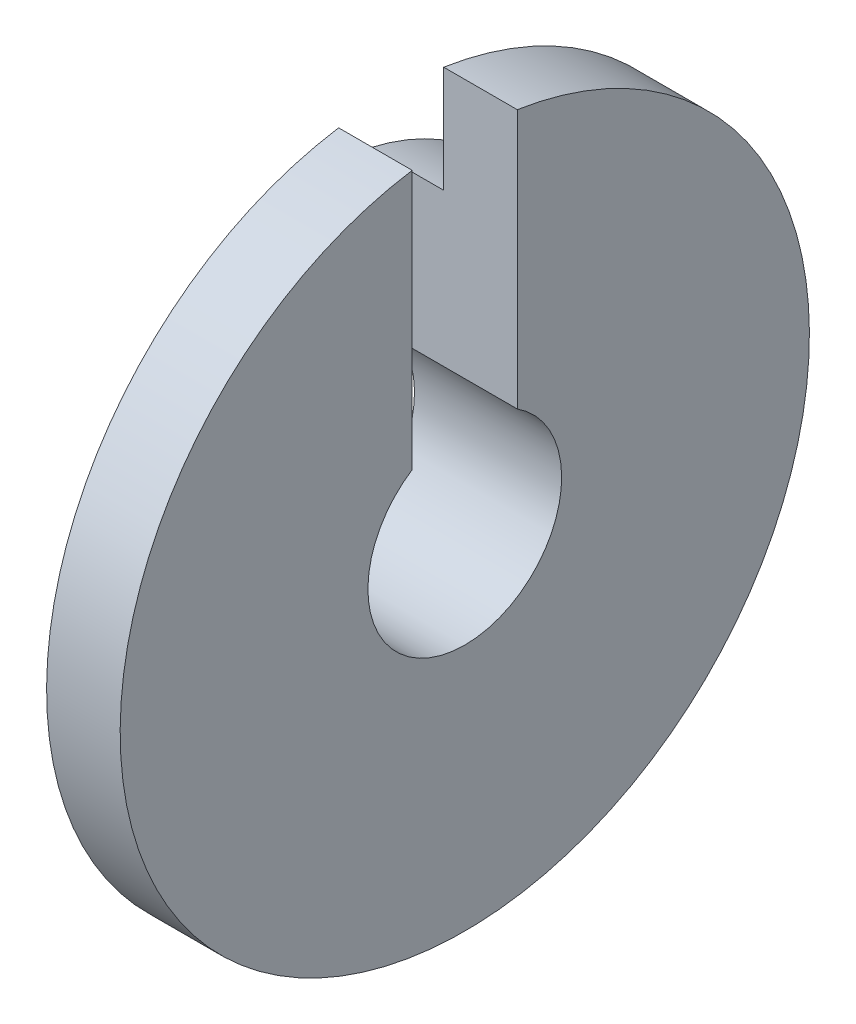
SolidWorks part; units mm, degrees
ref_plane "Front Plane" through (0, 0, 0) normal (0, 0, 1) x (1, 0, 0)
ref_plane "Top Plane" through (0, 0, 0) normal (0, 1, 0) x (1, 0, 0)
ref_plane "Right Plane" through (0, 0, 0) normal (1, 0, 0) x (0, 0, -1)
sketch "Sketch1" plane through (0, 0, 0) normal (1, 0, 0) x (0, 0, -1)
  line L2 (0.5435, 3.528) -> (0.5435, 0.8433)
  line L4 (-0.5445, 3.5279) -> (-0.5445, 0.8427)
  arc A0 (-0.5445, 0.8427) -> (0.5435, 0.8433) centre (0, 0) ccw
  arc A1 (-0.5445, 3.5279) -> (0.5435, 3.528) centre (0, 0) ccw
  point P4 (0, 2.8539)
extrude "Boss-Extrude1" add sketch "Sketch1" along normal blind 0.762
sketch "Sketch3" plane through (0.762, 0, 0) normal (1, 0, 0) x (0, 0, -1)
  line L0 (-0.5445, 2.4233) -> (-0.5445, 0.8427)
  line L1 (-0.5445, 0.8427) -> (-0.5445, 3.5279) construction
  line L2 (0.5435, 2.4236) -> (0.5435, 0.8433)
  line L3 (0.5435, 3.528) -> (0.5435, 0.8433) construction
  arc A0 (-0.5445, 2.4233) -> (0.5435, 2.4236) centre (0, 0) ccw
  arc A1 (-0.5445, 0.8427) -> (0.5435, 0.8433) centre (0, 0) ccw
extrude "Boss-Extrude2" add sketch "Sketch3" against normal blind 1.524
